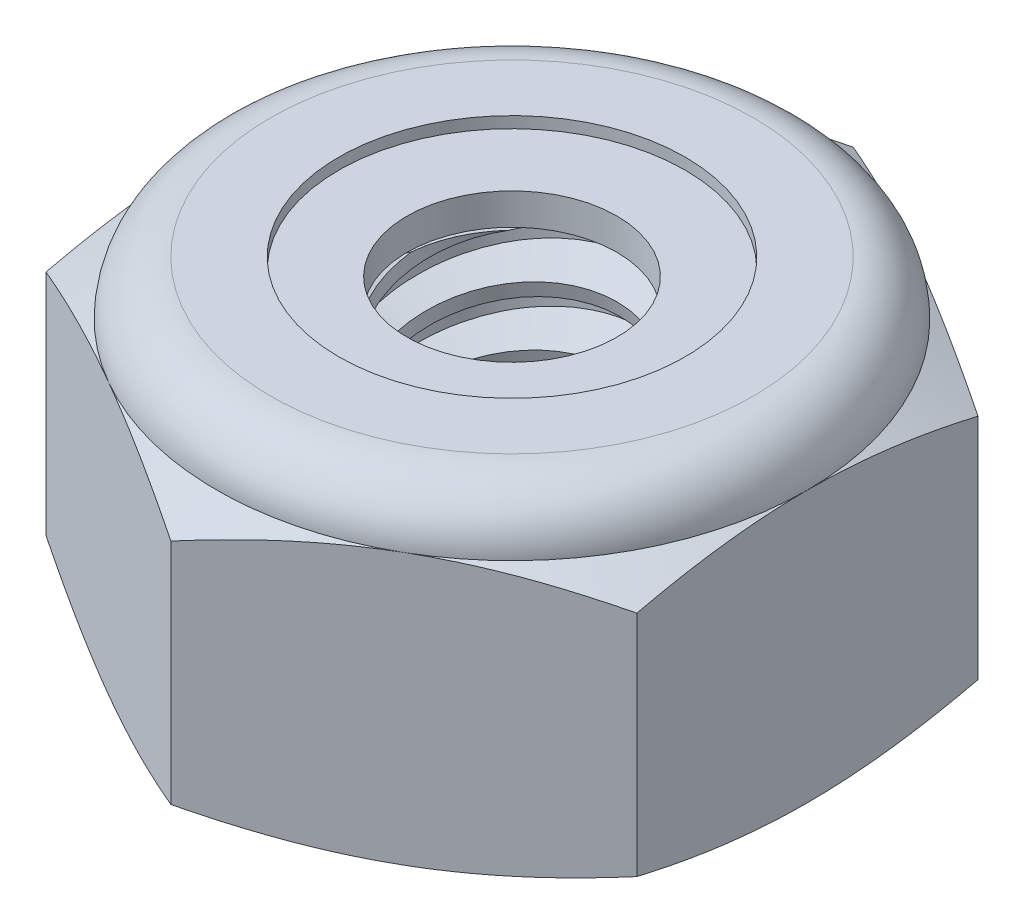
SolidWorks part; units mm, degrees
ref_plane "Front" through (0, 0, 0) normal (0, 0, 1) x (1, 0, 0)
ref_plane "Top" through (0, 0, 0) normal (0, 1, 0) x (1, 0, 0)
ref_plane "Right" through (0, 0, 0) normal (1, 0, 0) x (0, 0, -1)
sketch "Sketch1" plane through (0, 0, 0) normal (0, 1, 0) x (1, 0, 0)
  line L1 (0, 4.5827) -> (-3.9688, 2.2914)
  line L2 (-3.9688, 2.2914) -> (-3.9688, -2.2914)
  line L3 (-3.9688, -2.2914) -> (0, -4.5827)
  line L4 (0, -4.5827) -> (3.9687, -2.2914)
  line L5 (3.9687, -2.2914) -> (3.9687, 2.2914)
  line L6 (3.9687, 2.2914) -> (0, 4.5827)
  circle A0 centre (0, 0) radius 3.9688 construction
  dimension "Hex Flats" = 7.9375
extrude "Extrude1" add sketch "Sketch1" along normal blind 4.3656
sketch "Sketch2" plane through (0, 0, 0) normal (1, 0, 0) x (0, 0, -1)
  line L0 (-1.7526, 0) -> (-1.7526, 4.3656) construction
  line L1 (0, 0) -> (1.7526, 0)
  line L2 (0, 0) -> (0, 4.3656)
  line L3 (0, 4.3656) -> (1.7526, 4.3656)
  line L4 (1.7526, 0) -> (1.7526, 4.3656)
  line L5 (-2.2914, 4.3656) -> (2.2914, 4.3656) construction
  line L7 (0, -1.7526) -> (0, 0) construction
  dimension "Thread Dia" = 3.5052
revolve "Revolve1" add sketch "Sketch2" angle 360 about L7
sketch "Sketch3" plane through (0, 0, 0) normal (1, 0, 0) x (0, 0, -1)
  line L0 (1.7526, 4.3656) -> (-1.7526, 4.3656) construction
  line L1 (-1.7526, 4.3656) -> (-1.7526, 3.5719) construction
  line L2 (-1.7526, 3.5719) -> (1.7526, 4.3656) construction
  line L3 (1.7526, 4.3656) -> (1.7745, 4.2689) construction
  line L4 (1.7745, 4.2689) -> (1.9279, 3.5915)
  line L5 (1.9279, 3.5915) -> (1.4541, 3.7385)
  line L6 (1.4541, 3.7385) -> (1.4103, 3.932)
  line L7 (1.4103, 3.932) -> (1.7745, 4.2689)
  line L8 (1.4322, 3.8353) -> (1.8512, 3.9302) construction
  line L9 (1.7526, 4.3656) -> (1.7526, 3.9078) construction
  line L10 (1.7526, 3.9078) -> (-1.7526, 3.1141) construction
  line L11 (-1.7526, 3.1141) -> (-1.7526, 3.5719) construction
  line L12 (-0.1935, 4.3656) -> (0.1935, 2.6563) construction
  line L13 (-1.7526, 0) -> (-1.7526, 4.3656) construction
  line L14 (0, 4.3656) -> (1.7526, 4.3656) construction
  line L15 (1.7526, 0) -> (1.7526, 4.3656) construction
  point P13 (0, 3.511)
  dimension "D1" = 0.0992
  dimension "D2" = 0.1984
  dimension "Thread Pitch" = 0.7937
  dimension "D4" = 60
  dimension "D5" = 0.7937
revolve "Cut-Revolve1" cut sketch "Sketch3" angle 360 about L12
pattern_linear "LPattern1" count 6 spacing 0.7937 along (0, -1, 0) count 2 spacing 0.7937 along (0, 1, 0) of "Cut-Revolve1"
sketch "Sketch4" plane through (0, 0, 0) normal (1, 0, 0) x (0, 0, -1)
  line L0 (0, 4.3656) -> (1.7526, 4.3656)
  line L1 (1.7526, 4.3656) -> (1.4103, 4.206)
  line L2 (1.4103, 4.206) -> (1.4103, 0.1596)
  line L3 (1.4103, 0.1596) -> (1.7526, 0)
  line L4 (1.7526, 0) -> (0, 0)
  line L5 (0, 0) -> (0, 4.3656)
  line L6 (1.7526, 0) -> (1.7526, 4.3656) construction
  line L7 (0, 4.3656) -> (1.7526, 4.3656) construction
  line L8 (0, 0) -> (1.7526, 0) construction
  line L9 (0, 0) -> (0, 4.3656) construction
  line L10 (0, 4.3656) -> (0, 4.7433) construction
  dimension "D1" = 25
revolve "Cut-Revolve2" cut sketch "Sketch4" angle 360 about L10
combine bodies "Combine1" operation type subtract main body 112 bodies to subtract 111
sketch "Sketch5" plane through (0, 0, 0) normal (1, 0, 0) x (0, 0, -1)
  line L0 (0, 0) -> (3.9688, 0)
  line L1 (3.9688, 0) -> (4.5827, 0.2863)
  line L2 (4.5827, 0.2863) -> (4.5827, 3.3517)
  line L3 (4.5827, 3.3517) -> (3.9688, 3.638)
  line L4 (3.2411, 4.3656) -> (3.2411, 5.6356)
  line L5 (3.2411, 5.6356) -> (5.8527, 5.6356)
  line L6 (5.8527, 5.6356) -> (5.8527, -1.27)
  line L7 (5.8527, -1.27) -> (0, -1.27)
  line L8 (0, -1.27) -> (0, 0)
  line L9 (3.9688, 3.638) -> (3.9688, 0) construction
  line L10 (0, 0) -> (1.7526, 0) construction
  line L13 (4.5827, 1.819) -> (5.8527, 1.819) construction
  line L14 (4.5827, 4.3656) -> (4.5827, 0) construction
  line L15 (0, 0) -> (0, 5.6356) construction
  line L20 (0, 5.6356) -> (3.2411, 5.6356) construction
  line L22 (0, 4.3656) -> (1.7526, 4.3656) construction
  arc A0 (3.9688, 3.638) -> (3.2411, 4.3656) centre (3.2411, 3.638) ccw
  dimension "D1" = 25
  dimension "D2" = 1.27
  dimension "D3" = 4.3656
  dimension "D4" = 0.7276
revolve "Cut-Revolve3" cut sketch "Sketch5" angle 360 about L15
sketch "Sketch6" plane through (0, 0, 0) normal (1, 0, 0) x (0, 0, -1)
  line L0 (0, 3.638) -> (3.8164, 3.638)
  line L1 (3.2411, 4.2132) -> (2.3257, 4.2132)
  line L2 (0, 5.6356) -> (0, 3.638)
  line L3 (2.3257, 5.6356) -> (0, 5.6356)
  line L4 (0, 5.6356) -> (3.2411, 5.6356) construction
  line L5 (0, 0) -> (0, 5.6356) construction
  line L6 (0, 5.6356) -> (0, 44.323) construction
  line L7 (2.3257, 4.2132) -> (2.3257, 5.6356)
  line L8 (3.2411, 4.3656) -> (3.2411, 4.2132) construction
  line L9 (2.3257, 4.2132) -> (1.4103, 4.2132) construction
  line L10 (1.4103, 4.2132) -> (1.4103, 4.206) construction
  arc A0 (3.8164, 3.638) -> (3.2411, 4.2132) centre (3.2411, 3.638) ccw
  arc A1 (3.9688, 3.638) -> (3.2411, 4.3656) centre (3.2411, 3.638) ccw construction
  dimension "D1" = 0.1524
revolve "Cut-Revolve4" cut sketch "Sketch6" angle 360 about L6
sketch "Sketch7" plane through (0, 0, 0) normal (1, 0, 0) x (0, 0, -1)
  line L0 (1.4103, 3.7142) -> (3.7343, 3.7142)
  line L1 (3.2411, 4.137) -> (1.4103, 4.137)
  line L2 (1.4103, 4.137) -> (1.4103, 3.7142)
  line L3 (1.4103, 3.7142) -> (0, 3.7142) construction
  line L4 (0, 3.7142) -> (0, 4.137) construction
  line L5 (0, 4.137) -> (1.4103, 4.137) construction
  line L6 (1.4103, 3.7142) -> (1.4103, 3.638) construction
  line L7 (0, 3.638) -> (3.8164, 3.638) construction
  line L8 (3.2411, 4.137) -> (3.2411, 4.2132) construction
  arc A0 (3.7343, 3.7142) -> (3.2411, 4.137) centre (3.2411, 3.638) ccw
  arc A2 (3.8164, 3.638) -> (3.2411, 4.2132) centre (3.2411, 3.638) ccw construction
  dimension "D1" = 0.0762
revolve "Revolve2" add sketch "Sketch7" angle 360 about L4
equation "\"D1@Sketch3\"=\"Thread Pitch@Sketch3\"/8"
equation "\"D2@Sketch3\"=\"Thread Pitch@Sketch3\"/4"
equation "\"D5@Sketch3\"=\"Thread Pitch@Sketch3\""
equation "\"D4@LPattern1\"=\"Thread Pitch@Sketch3\""
equation "\"D3@LPattern1\"=\"Thread Pitch@Sketch3\""
equation "\"D1@LPattern1\"=\"Height@Extrude1\"/\"Thread Pitch@Sketch3\""
equation "\"D4@Sketch5\"=\"Height@Extrude1\"/6"
